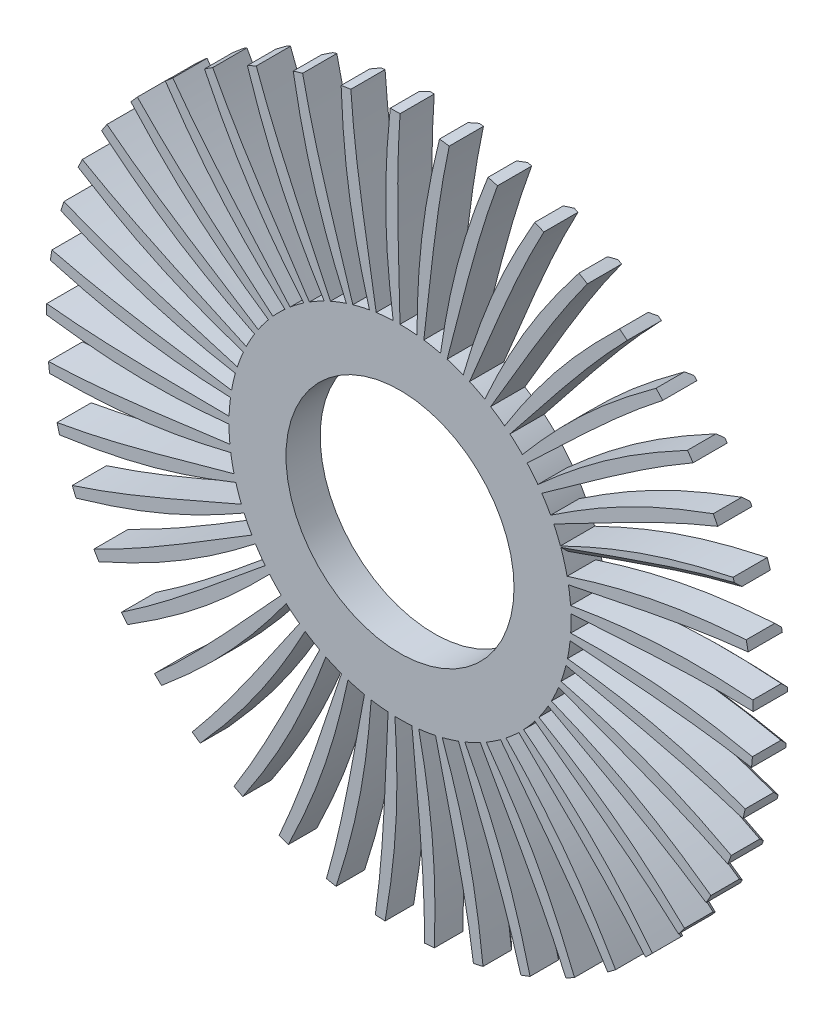
SolidWorks part; units mm, degrees
ref_plane "Front Plane" through (0, 0, 0) normal (0, 0, 1) x (1, 0, 0)
ref_plane "Top Plane" through (0, 0, 0) normal (0, 1, 0) x (1, 0, 0)
ref_plane "Right Plane" through (0, 0, 0) normal (1, 0, 0) x (0, 0, -1)
sketch "Sketch2" plane through (0, 0, 0) normal (0, 0, 1) x (1, 0, 0)
  arc A0 (-145.5697, -273.6959) -> (-137.9022, -277.6382) centre (0, 0) ccw
  arc A1 (-6, 149.88) -> (-20.876, 148.5402) centre (0, 0) ccw
  arc A2 (-106.0619, -291.2917) -> (-97.9204, -294.1285) centre (0, 0) ccw
  arc A3 (-64.4898, -303.2179) -> (-56.0327, -304.894) centre (0, 0) ccw
  arc A4 (-21.6624, -309.2422) -> (-13.0543, -309.725) centre (0, 0) ccw
  arc A5 (21.5866, -309.2475) -> (30.1781, -308.5276) centre (0, 0) ccw
  arc A6 (64.4155, -303.2336) -> (72.8232, -301.3251) centre (0, 0) ccw
  arc A7 (105.9906, -291.3177) -> (114.0508, -288.2576) centre (0, 0) ccw
  arc A8 (145.5027, -273.7316) -> (153.0586, -269.5794) centre (0, 0) ccw
  arc A9 (215.3168, -223.0217) -> (221.4355, -216.9477) centre (0, 0) ccw
  arc A10 (182.1827, -250.8176) -> (189.0872, -245.6543) centre (0, 0) ccw
  arc A11 (244.26, -190.885) -> (249.4738, -184.0186) centre (0, 0) ccw
  arc A12 (268.4489, -155.0329) -> (272.6564, -147.5077) centre (0, 0) ccw
  arc A13 (300.7825, -75.0326) -> (302.7527, -66.6392) centre (0, 0) ccw
  arc A14 (308.2978, -32.4416) -> (309.0807, -23.8556) centre (0, 0) ccw
  arc A15 (309.8125, 10.7809) -> (309.3929, 19.3923) centre (0, 0) ccw
  arc A16 (305.297, 53.7936) -> (303.683, 62.2627) centre (0, 0) ccw
  arc A17 (294.8392, 95.7592) -> (292.0623, 103.9213) centre (0, 0) ccw
  arc A18 (278.6428, 135.8609) -> (274.7569, 143.5571) centre (0, 0) ccw
  arc A19 (257.0229, 173.3183) -> (252.1037, 180.3988) centre (0, 0) ccw
  arc A20 (230.4003, 207.4023) -> (224.5436, 213.7292) centre (0, 0) ccw
  arc A21 (199.2932, 237.4494) -> (192.613, 242.8997) centre (0, 0) ccw
  arc A22 (164.3072, 262.8748) -> (156.9334, 267.3423) centre (0, 0) ccw
  arc A23 (126.123, 283.1837) -> (118.1992, 286.5815) centre (0, 0) ccw
  arc A24 (85.4841, 297.9807) -> (77.1645, 300.2426) centre (0, 0) ccw
  arc A25 (43.1813, 306.9778) -> (34.6279, 308.0599) centre (0, 0) ccw
  arc A26 (0.038, 310) -> (-8.5828, 309.8812) centre (0, 0) ccw
  arc A27 (-43.1061, 306.9884) -> (-51.6264, 305.6709) centre (0, 0) ccw
  arc A28 (-85.4111, 298.0016) -> (-93.6651, 295.5112) centre (0, 0) ccw
  arc A29 (-126.0537, 283.2145) -> (-133.8808, 279.5996) centre (0, 0) ccw
  arc A30 (-164.2428, 262.915) -> (-171.4906, 258.2459) centre (0, 0) ccw
  arc A31 (-199.2351, 237.4982) -> (-205.7626, 231.8658) centre (0, 0) ccw
  arc A32 (-230.3495, 207.4587) -> (-236.0296, 200.9727) centre (0, 0) ccw
  arc A33 (-256.9804, 173.3813) -> (-261.7026, 166.1679) centre (0, 0) ccw
  arc A34 (-278.6095, 135.9292) -> (-282.2818, 128.1288) centre (0, 0) ccw
  arc A35 (-294.8158, 95.8314) -> (-297.3667, 87.5958) centre (0, 0) ccw
  arc A36 (-305.2838, 53.8683) -> (-306.6638, 45.3579) centre (0, 0) ccw
  arc A37 (-309.8098, 10.8568) -> (-309.9919, 2.2371) centre (0, 0) ccw
  arc A38 (-308.3058, -32.3661) -> (-307.2865, -40.9272) centre (0, 0) ccw
  arc A39 (-300.8009, -74.959) -> (-298.6, -83.2949) centre (0, 0) ccw
  arc A40 (-287.4412, -116.0928) -> (-284.1016, -124.0414) centre (0, 0) ccw
  arc A41 (-268.4869, -154.9671) -> (-264.0736, -162.3735) centre (0, 0) ccw
  arc A42 (-244.3067, -190.8251) -> (-238.9056, -197.5452) centre (0, 0) ccw
  arc A43 (-215.3714, -222.969) -> (-209.0876, -228.872) centre (0, 0) ccw
  arc A44 (287.4128, -116.1632) -> (290.532, -108.1257) centre (0, 0) ccw
  arc A46 (-26.8009, 147.5863) -> (-41.3456, 144.1893) centre (0, 0) ccw
  arc A47 (-47.0801, 142.42) -> (-61.0105, 137.0318) centre (0, 0) ccw
  arc A48 (35.5449, 145.7277) -> (20.876, 148.5402) centre (0, 0) ccw
  arc A49 (14.9176, 149.2564) -> (0, 150) centre (0, 0) ccw
  arc A50 (-66.4429, 134.4817) -> (-79.4879, 127.2072) centre (0, 0) ccw
  arc A51 (-84.5126, 123.9259) -> (-96.4181, 114.9067) centre (0, 0) ccw
  arc A52 (-100.9372, 110.958) -> (-111.4717, 100.3696) centre (0, 0) ccw
  arc A53 (55.4804, 139.3626) -> (41.3456, 144.1893) centre (0, 0) ccw
  arc A54 (74.336, 130.2849) -> (61.0105, 137.0318) centre (0, 0) ccw
  arc A55 (91.7447, 118.6714) -> (79.4879, 127.2072) centre (0, 0) ccw
  arc A56 (-115.3973, 95.8304) -> (-124.3556, 83.8789) centre (0, 0) ccw
  arc A57 (-127.6113, 78.8376) -> (-134.8191, 65.7557) centre (0, 0) ccw
  arc A58 (107.3677, 104.7481) -> (96.4181, 114.9067) centre (0, 0) ccw
  arc A59 (120.901, 88.786) -> (111.4717, 100.3696) centre (0, 0) ccw
  arc A60 (132.081, 71.0958) -> (124.3556, 83.8789) centre (0, 0) ccw
  arc A61 (-137.3414, 60.3103) -> (-142.6585, 46.3525) centre (0, 0) ccw
  arc A62 (140.6902, 52.0218) -> (134.8191, 65.7557) centre (0, 0) ccw
  arc A63 (146.561, 31.9352) -> (142.6585, 46.3525) centre (0, 0) ccw
  arc A64 (-144.3984, 40.6091) -> (-147.7212, 26.0472) centre (0, 0) ccw
  arc A65 (-148.6448, 20.1175) -> (-149.9086, 5.2349) centre (0, 0) ccw
  arc A66 (-149.998, -0.7656) -> (-149.1783, -15.6793) centre (0, 0) ccw
  arc A67 (-148.4317, -21.6339) -> (-145.5444, -36.2883) centre (0, 0) ccw
  arc A68 (-143.9763, -42.081) -> (-139.0776, -56.191) centre (0, 0) ccw
  arc A69 (-136.7186, -61.7091) -> (-129.9038, -75) centre (0, 0) ccw
  arc A70 (-126.7998, -80.1361) -> (-118.2016, -92.3492) centre (0, 0) ccw
  arc A71 (-114.413, -97.0034) -> (-104.1988, -107.901) centre (0, 0) ccw
  arc A72 (-99.7993, -111.9826) -> (-88.1678, -121.3525) centre (0, 0) ccw
  arc A73 (-83.2431, -124.7821) -> (-70.4207, -132.4421) centre (0, 0) ccw
  arc A74 (-65.0667, -135.153) -> (-51.303, -140.9539) centre (0, 0) ccw
  arc A75 (-45.6238, -142.8932) -> (-31.1868, -146.7221) centre (0, 0) ccw
  arc A76 (-25.2929, -147.8522) -> (-10.4635, -149.6346) centre (0, 0) ccw
  arc A77 (-4.4697, -149.9334) -> (10.4635, -149.6346) centre (0, 0) ccw
  arc A78 (16.4405, -149.0963) -> (31.1868, -146.7221) centre (0, 0) ccw
  arc A79 (37.0307, -145.3572) -> (51.303, -140.9539) centre (0, 0) ccw
  arc A80 (56.9001, -138.789) -> (70.4207, -132.4421) centre (0, 0) ccw
  arc A81 (75.6621, -129.5193) -> (88.1678, -121.3525) centre (0, 0) ccw
  arc A82 (108.4314, -103.6467) -> (118.2016, -92.3492) centre (0, 0) ccw
  arc A83 (121.801, -87.5472) -> (129.9038, -75) centre (0, 0) ccw
  arc A84 (132.7998, -69.7438) -> (139.0776, -56.191) centre (0, 0) ccw
  arc A85 (141.2139, -50.5829) -> (145.5444, -36.2883) centre (0, 0) ccw
  arc A86 (146.8794, -30.4375) -> (149.1783, -15.6793) centre (0, 0) ccw
  arc A87 (92.9513, -117.7287) -> (104.1988, -107.901) centre (0, 0) ccw
  arc A88 (149.6861, -9.6996) -> (149.9086, 5.2349) centre (0, 0) ccw
  arc A89 (149.5793, 11.2271) -> (147.7212, 26.0472) centre (0, 0) ccw
  arc A90 (-182.2441, -250.773) -> (-175.1999, -255.744) centre (0, 0) ccw
  spline S0 degree 3 poles (-6, 149.88) (-14.7384, 213.1207) (-13.9604, 257.3784) (-8.5828, 309.8812) knots 0 0 0 0 0.636597 0.636597 0.636597 0.636597
  spline S1 degree 3 poles (0, 150) (-1.1325, 204.7695) (-3.9165, 255.516) (0.038, 310) knots 0 0 0 0 0.656299 0.656299 0.656299 0.656299
  spline S2 degree 3 poles (14.9176, 149.2564) (15.0657, 213.0978) (21.9957, 256.8165) (34.6279, 308.0599) knots 0 0 0 0 0.636597 0.636597 0.636597 0.636597
  spline S3 degree 3 poles (20.876, 148.5402) (27.3769, 202.9343) (31.6826, 253.5744) (43.1813, 306.9778) knots 0 0 0 0 0.656299 0.656299 0.656299 0.656299
  spline S4 degree 3 poles (35.5449, 145.7277) (44.5765, 208.9272) (57.5235, 251.256) (77.1645, 300.2426) knots 0 0 0 0 0.636597 0.636597 0.636597 0.636597
  spline S5 degree 3 poles (41.3456, 144.1893) (55.3535, 197.1492) (66.665, 246.6973) (85.4841, 297.9807) knots 0 0 0 0 0.656299 0.656299 0.656299 0.656299
  spline S6 degree 3 poles (55.4804, 139.3626) (73.2198, 200.6901) (91.9318, 240.8051) (118.1992, 286.5815) knots 0 0 0 0 0.636597 0.636597 0.636597 0.636597
  spline S7 degree 3 poles (61.0105, 137.0318) (82.2527, 187.5269) (100.3498, 235.0185) (126.123, 283.1837) knots 0 0 0 0 0.656299 0.656299 0.656299 0.656299
  spline S8 degree 3 poles (74.336, 130.2849) (100.4379, 188.5468) (124.5507, 225.6671) (156.9334, 267.3423) knots 0 0 0 0 0.636597 0.636597 0.636597 0.636597
  spline S9 degree 3 poles (79.4879, 127.2072) (107.5509, 174.2545) (132.0815, 218.7653) (164.3072, 262.8748) knots 0 0 0 0 0.656299 0.656299 0.656299 0.656299
  spline S10 degree 3 poles (91.7447, 118.6714) (125.701, 172.7336) (154.7454, 206.1368) (192.613, 242.8997) knots 0 0 0 0 0.636597 0.636597 0.636597 0.636597
  spline S11 degree 3 poles (96.4181, 114.9067) (130.7557, 157.5905) (161.2423, 198.2541) (199.2932, 237.4494) knots 0 0 0 0 0.656299 0.656299 0.656299 0.656299
  spline S12 degree 3 poles (107.3677, 104.7481) (148.5176, 153.5584) (181.9281, 182.5943) (224.5436, 213.7292) knots 0 0 0 0 0.636597 0.636597 0.636597 0.636597
  spline S13 degree 3 poles (111.4717, 100.3696) (151.4156, 137.8592) (187.2648, 173.8841) (230.4003, 207.4023) knots 0 0 0 0 0.656299 0.656299 0.656299 0.656299
  spline S14 degree 3 poles (120.901, 88.786) (168.4434, 131.3943) (205.5698, 155.4978) (252.1037, 180.3988) knots 0 0 0 0 0.636597 0.636597 0.636597 0.636597
  spline S15 degree 3 poles (124.3556, 83.8789) (169.1283, 115.4445) (209.6423, 146.1297) (257.0229, 173.3183) knots 0 0 0 0 0.656299 0.656299 0.656299 0.656299
  spline S16 degree 3 poles (132.081, 71.0958) (185.0907, 106.6728) (225.2104, 125.3748) (274.7569, 143.5571) knots 0 0 0 0 0.636597 0.636597 0.636597 0.636597
  spline S17 degree 3 poles (134.8191, 65.7557) (183.5491, 90.7829) (227.9394, 115.531) (278.6428, 135.8609) knots 0 0 0 0 0.656299 0.656299 0.656299 0.656299
  spline S18 degree 3 poles (140.6902, 52.0218) (198.1354, 79.875) (240.4674, 92.8114) (292.0623, 103.9213) knots 0 0 0 0 0.636597 0.636597 0.636597 0.636597
  spline S19 degree 3 poles (142.6585, 46.3525) (194.3974, 64.3543) (241.7999, 82.6836) (294.8392, 95.7592) knots 0 0 0 0 0.656299 0.656299 0.656299 0.656299
  spline S20 degree 3 poles (146.561, 31.9352) (207.3236, 51.5225) (251.0441, 58.4416) (303.683, 62.2627) knots 0 0 0 0 0.636597 0.636597 0.636597 0.636597
  spline S21 degree 3 poles (147.7212, 26.0472) (201.4619, 36.6732) (250.9541, 48.2269) (305.297, 53.7936) knots 0 0 0 0 0.656299 0.656299 0.656299 0.656299
  spline S22 degree 3 poles (149.5793, 11.2271) (212.4765, 22.1673) (256.7344, 22.9342) (309.3929, 19.3923) knots 0 0 0 0 0.636597 0.636597 0.636597 0.636597
  spline S23 degree 3 poles (149.9086, 5.2349) (204.6052, 8.2782) (255.2237, 12.8315) (309.8125, 10.7809) knots 0 0 0 0 0.656299 0.656299 0.656299 0.656299
  spline S24 degree 3 poles (149.6861, -9.6996) (213.4938, -7.6195) (257.4277, -13.0195) (309.0807, -23.8556) knots 0 0 0 0 0.636597 0.636597 0.636597 0.636597
  spline S25 degree 3 poles (149.1783, -15.6793) (203.7661, -20.2779) (254.5257, -22.8137) (308.2978, -32.4416) knots 0 0 0 0 0.656299 0.656299 0.656299 0.656299
  spline S26 degree 3 poles (146.8794, -30.4375) (210.3556, -37.2579) (253.1105, -48.7198) (302.7527, -66.6392) knots 0 0 0 0 0.636597 0.636597 0.636597 0.636597
  spline S27 degree 3 poles (145.5444, -36.2883) (198.9609, -48.4394) (248.8736, -58.0148) (300.7825, -75.0326) knots 0 0 0 0 0.656299 0.656299 0.656299 0.656299
  spline S28 degree 3 poles (141.2139, -50.5829) (203.1232, -66.1712) (243.8667, -83.4718) (290.532, -108.1257) knots 0 0 0 0 0.636597 0.636597 0.636597 0.636597
  spline S29 degree 3 poles (139.0776, -56.191) (190.2832, -75.658) (238.3775, -92.0867) (287.4128, -116.1632) knots 0 0 0 0 0.656299 0.656299 0.656299 0.656299
  spline S30 degree 3 poles (132.7998, -69.7438) (191.9371, -93.7965) (229.8764, -116.5992) (272.6564, -147.5077) knots 0 0 0 0 0.636597 0.636597 0.636597 0.636597
  spline S31 degree 3 poles (129.9038, -75) (177.9018, -101.404) (223.2416, -124.3662) (268.4489, -155.0329) knots 0 0 0 0 0.656299 0.656299 0.656299 0.656299
  spline S32 degree 3 poles (121.801, -87.5472) (177.0153, -119.5962) (211.4118, -147.4571) (249.4738, -184.0186) knots 0 0 0 0 0.636597 0.636597 0.636597 0.636597
  spline S33 degree 3 poles (118.2016, -92.3492) (162.0578, -125.1763) (203.7606, -154.2251) (244.26, -190.885) knots 0 0 0 0 0.656299 0.656299 0.656299 0.656299
  spline S34 degree 3 poles (108.4314, -103.6467) (158.648, -143.068) (188.8323, -175.4448) (221.4355, -216.9477) knots 0 0 0 0 0.636597 0.636597 0.636597 0.636597
  spline S35 degree 3 poles (104.1988, -107.901) (143.0595, -146.5121) (180.3137, -181.0822) (215.3168, -223.0217) knots 0 0 0 0 0.656299 0.656299 0.656299 0.656299
  spline S36 degree 3 poles (92.9513, -117.7287) (137.1928, -163.7552) (162.5774, -200.0178) (189.0872, -245.6543) knots 0 0 0 0 0.636597 0.636597 0.636597 0.636597
  spline S37 degree 3 poles (88.1678, -121.3525) (121.2767, -164.9963) (153.3571, -204.4148) (182.1827, -250.8176) knots 0 0 0 0 0.656299 0.656299 0.656299 0.656299
  spline S38 degree 3 poles (75.6621, -129.5193) (113.0674, -181.2551) (133.1581, -220.6977) (153.0586, -269.5794) knots 0 0 0 0 0.636597 0.636597 0.636597 0.636597
  spline S39 degree 3 poles (70.4207, -132.4421) (97.1334, -180.269) (123.4156, -223.7686) (145.5027, -273.7316) knots 0 0 0 0 0.656299 0.656299 0.656299 0.656299
  spline S40 degree 3 poles (56.9001, -138.789) (86.7412, -195.2271) (101.147, -237.0819) (114.0508, -288.2576) knots 0 0 0 0 0.636597 0.636597 0.636597 0.636597
  spline S41 degree 3 poles (51.303, -140.9539) (71.0995, -192.033) (91.0719, -238.767) (105.9906, -291.3177) knots 0 0 0 0 0.656299 0.656299 0.656299 0.656299
  spline S42 degree 3 poles (37.0307, -145.3572) (58.7266, -205.3992) (67.1673, -248.8515) (72.8232, -301.3251) knots 0 0 0 0 0.636597 0.636597 0.636597 0.636597
  spline S43 degree 3 poles (31.1868, -146.7221) (43.6817, -200.0593) (56.9557, -249.1181) (64.4155, -303.2336) knots 0 0 0 0 0.656299 0.656299 0.656299 0.656299
  spline S44 degree 3 poles (16.4405, -149.0963) (29.5691, -211.5734) (31.8802, -255.7776) (30.1781, -308.5276) knots 0 0 0 0 0.636597 0.636597 0.636597 0.636597
  spline S45 degree 3 poles (10.4635, -149.6346) (15.4137, -204.1917) (21.7309, -254.6204) (21.5866, -309.2475) knots 0 0 0 0 0.656299 0.656299 0.656299 0.656299
  spline S46 degree 3 poles (-4.4697, -149.9334) (-0.164, -213.6296) (-4.0275, -257.7253) (-13.0543, -309.725) knots 0 0 0 0 0.636597 0.636597 0.636597 0.636597
  spline S47 degree 3 poles (-10.4635, -149.6346) (-13.1542, -204.3497) (-13.9169, -255.1668) (-21.6624, -309.2422) knots 0 0 0 0 0.656299 0.656299 0.656299 0.656299
  spline S48 degree 3 poles (-25.2929, -147.8522) (-29.8939, -211.5278) (-39.8567, -254.6566) (-56.0327, -304.894) knots 0 0 0 0 0.636597 0.636597 0.636597 0.636597
  spline S49 degree 3 poles (-31.1868, -146.7221) (-41.4662, -200.5302) (-49.2939, -250.7467) (-64.4898, -303.2179) knots 0 0 0 0 0.656299 0.656299 0.656299 0.656299
  spline S50 degree 3 poles (-45.6238, -142.8932) (-59.042, -205.3088) (-74.9102, -246.6313) (-97.9204, -294.1285) knots 0 0 0 0 0.636597 0.636597 0.636597 0.636597
  spline S51 degree 3 poles (-51.303, -140.9539) (-68.9711, -192.8077) (-83.7113, -241.4461) (-106.0619, -291.2917) knots 0 0 0 0 0.656299 0.656299 0.656299 0.656299
  spline S52 degree 3 poles (-65.0667, -135.153) (-87.0408, -195.0937) (-108.5056, -233.8056) (-137.9022, -277.6382) knots 0 0 0 0 0.636597 0.636597 0.636597 0.636597
  spline S53 degree 3 poles (-70.4207, -132.4421) (-95.1335, -181.3324) (-116.4994, -227.446) (-145.5697, -273.6959) knots 0 0 0 0 0.656299 0.656299 0.656299 0.656299
  spline S54 degree 3 poles (-83.2431, -124.7821) (-113.3456, -181.0813) (-139.9891, -216.4292) (-175.1999, -255.744) knots 0 0 0 0 0.636597 0.636597 0.636597 0.636597
  spline S55 degree 3 poles (-88.1678, -121.3525) (-119.4443, -166.3277) (-147.02, -209.0189) (-182.2441, -250.773) knots 0 0 0 0 0.656299 0.656299 0.656299 0.656299
  spline S56 degree 3 poles (-99.7993, -111.9826) (-137.4441, -163.5444) (-168.7478, -194.8402) (-209.0876, -228.872) knots 0 0 0 0 0.636597 0.636597 0.636597 0.636597
  spline S57 degree 3 poles (-104.1988, -107.901) (-141.4302, -148.0856) (-174.6791, -186.5235) (-215.3714, -222.969) knots 0 0 0 0 0.656299 0.656299 0.656299 0.656299
  spline S58 degree 3 poles (-114.413, -97.0034) (-158.8675, -142.8242) (-194.2221, -169.4589) (-238.9056, -197.5452) knots 0 0 0 0 0.636597 0.636597 0.636597 0.636597
  spline S59 degree 3 poles (-118.2016, -92.3492) (-160.6633, -126.9611) (-198.9381, -160.3976) (-244.3067, -190.8251) knots 0 0 0 0 0.656299 0.656299 0.656299 0.656299
  spline S60 degree 3 poles (-126.7998, -80.1361) (-177.1987, -119.3242) (-215.9161, -140.7792) (-264.0736, -162.3735) knots 0 0 0 0 0.636597 0.636597 0.636597 0.636597
  spline S61 degree 3 poles (-129.9038, -75) (-176.7693, -103.3655) (-219.3251, -131.1498) (-268.4869, -154.9671) knots 0 0 0 0 0.656299 0.656299 0.656299 0.656299
  spline S62 degree 3 poles (-136.7186, -61.7091) (-192.0809, -93.5016) (-233.4075, -109.3595) (-284.1016, -124.0414) knots 0 0 0 0 0.636597 0.636597 0.636597 0.636597
  spline S63 degree 3 poles (-139.0776, -56.191) (-189.4347, -77.758) (-235.4432, -99.3493) (-287.4412, -116.0928) knots 0 0 0 0 0.656299 0.656299 0.656299 0.656299
  spline S64 degree 3 poles (-143.9763, -42.081) (-203.2245, -65.8592) (-246.3558, -75.8111) (-298.6, -83.2949) knots 0 0 0 0 0.636597 0.636597 0.636597 0.636597
  spline S65 degree 3 poles (-145.5444, -36.2883) (-198.413, -50.6371) (-246.9786, -65.6151) (-300.8009, -74.959) knots 0 0 0 0 0.656299 0.656299 0.656299 0.656299
  spline S66 degree 3 poles (-148.4317, -21.6339) (-210.4126, -36.9349) (-254.5092, -40.7873) (-307.2865, -40.9272) knots 0 0 0 0 0.636597 0.636597 0.636597 0.636597
  spline S67 degree 3 poles (-149.1783, -15.6793) (-203.5294, -22.5305) (-253.7069, -30.6037) (-308.3058, -32.3661) knots 0 0 0 0 0.656299 0.656299 0.656299 0.656299
  spline S68 degree 3 poles (-149.998, -0.7656) (-213.5052, -7.2916) (-257.7088, -4.9695) (-309.9919, 2.2371) knots 0 0 0 0 0.636597 0.636597 0.636597 0.636597
  spline S69 degree 3 poles (-149.9086, 5.2349) (-204.6843, 6.0145) (-255.4971, 5.0033) (-309.8098, 10.8568) knots 0 0 0 0 0.656299 0.656299 0.656299 0.656299
  spline S70 degree 3 poles (-148.6448, 20.1175) (-212.4422, 22.4935) (-255.8924, 30.945) (-306.6638, 45.3579) knots 0 0 0 0 0.636597 0.636597 0.636597 0.636597
  spline S71 degree 3 poles (-147.7212, 26.0472) (-201.8552, 34.4425) (-252.3143, 40.5129) (-305.2838, 53.8683) knots 0 0 0 0 0.656299 0.656299 0.656299 0.656299
  spline S72 degree 3 poles (-144.3984, 40.6091) (-207.2442, 51.8408) (-249.0954, 66.2572) (-297.3667, 87.5958) knots 0 0 0 0 0.636597 0.636597 0.636597 0.636597
  spline S73 degree 3 poles (-142.6585, 46.3525) (-195.0973, 62.2002) (-244.2205, 75.234) (-294.8158, 95.8314) knots 0 0 0 0 0.656299 0.656299 0.656299 0.656299
  spline S74 degree 3 poles (-137.3414, 60.3103) (-198.0125, 80.1791) (-237.45, 100.2798) (-282.2818, 128.1288) knots 0 0 0 0 0.636597 0.636597 0.636597 0.636597
  spline S75 degree 3 poles (-134.8191, 65.7557) (-184.5421, 88.7471) (-231.3732, 108.4907) (-278.6095, 135.9292) knots 0 0 0 0 0.656299 0.656299 0.656299 0.656299
  spline S76 degree 3 poles (-127.6113, 78.8376) (-184.9267, 106.9569) (-221.1829, 132.3505) (-261.7026, 166.1679) knots 0 0 0 0 0.636597 0.636597 0.636597 0.636597
  spline S77 degree 3 poles (-124.3556, 83.8789) (-170.3949, 113.5668) (-214.0225, 139.6358) (-256.9804, 173.3813) knots 0 0 0 0 0.656299 0.656299 0.656299 0.656299
  spline S78 degree 3 poles (-115.3973, 95.8304) (-168.2415, 131.6528) (-200.6107, 161.8452) (-236.0296, 200.9727) knots 0 0 0 0 0.636597 0.636597 0.636597 0.636597
  spline S79 degree 3 poles (-111.4717, 100.3696) (-152.9312, 136.1759) (-192.5061, 168.0631) (-230.3495, 207.4587) knots 0 0 0 0 0.656299 0.656299 0.656299 0.656299
  spline S80 degree 3 poles (-100.9372, 110.958) (-148.2816, 153.7862) (-176.1339, 188.1898) (-205.7626, 231.8658) knots 0 0 0 0 0.636597 0.636597 0.636597 0.636597
  spline S81 degree 3 poles (-96.4181, 114.9067) (-132.4908, 156.1346) (-167.2428, 193.2192) (-199.2351, 237.4982) knots 0 0 0 0 0.656299 0.656299 0.656299 0.656299
  spline S82 degree 3 poles (-84.5126, 123.9259) (-125.4357, 172.9264) (-148.2288, 210.8714) (-171.4906, 258.2459) knots 0 0 0 0 0.636597 0.636597 0.636597 0.636597
  spline S83 degree 3 poles (-79.4879, 127.2072) (-109.4717, 173.0542) (-138.7243, 214.6145) (-164.2428, 262.915) knots 0 0 0 0 0.656299 0.656299 0.656299 0.656299
  spline S84 degree 3 poles (-66.4429, 134.4817) (-100.1482, 188.7008) (-117.4386, 229.4487) (-133.8808, 279.5996) knots 0 0 0 0 0.636597 0.636597 0.636597 0.636597
  spline S85 degree 3 poles (-61.0105, 137.0318) (-84.3219, 186.6056) (-107.5056, 231.8325) (-126.0537, 283.2145) knots 0 0 0 0 0.656299 0.656299 0.656299 0.656299
  spline S86 degree 3 poles (-47.0801, 142.42) (-72.9115, 200.8023) (-84.3627, 243.56) (-93.6651, 295.5112) knots 0 0 0 0 0.636597 0.636597 0.636597 0.636597
  spline S87 degree 3 poles (-41.3456, 144.1893) (-57.5308, 196.5249) (-74.1945, 244.5382) (-85.4111, 298.0016) knots 0 0 0 0 0.656299 0.656299 0.656299 0.656299
  spline S88 degree 3 poles (-26.8009, 147.5863) (-44.2557, 208.9954) (-49.6446, 252.9307) (-51.6264, 305.6709) knots 0 0 0 0 0.636597 0.636597 0.636597 0.636597
  spline S89 degree 3 poles (-20.876, 148.5402) (-29.6199, 202.6191) (-39.4393, 252.4843) (-43.1061, 306.9884) knots 0 0 0 0 0.656299 0.656299 0.656299 0.656299
  point P230 (0, 0)
  dimension "D2" = 300
  dimension "D3" = 45
extrude "Boss-Extrude1" add sketch "Sketch2" along normal blind 30
chamfer "Chamfer1" distance 5 angle 45 45 edges
sketch "Sketch4" plane through (0, 0, 30) normal (0, 0, 1) x (1, 0, 0)
  circle A0 centre (0, 0) radius 100
  dimension "D1" = 200
extrude "Cut-Extrude4" cut sketch "Sketch4" against normal blind 30
